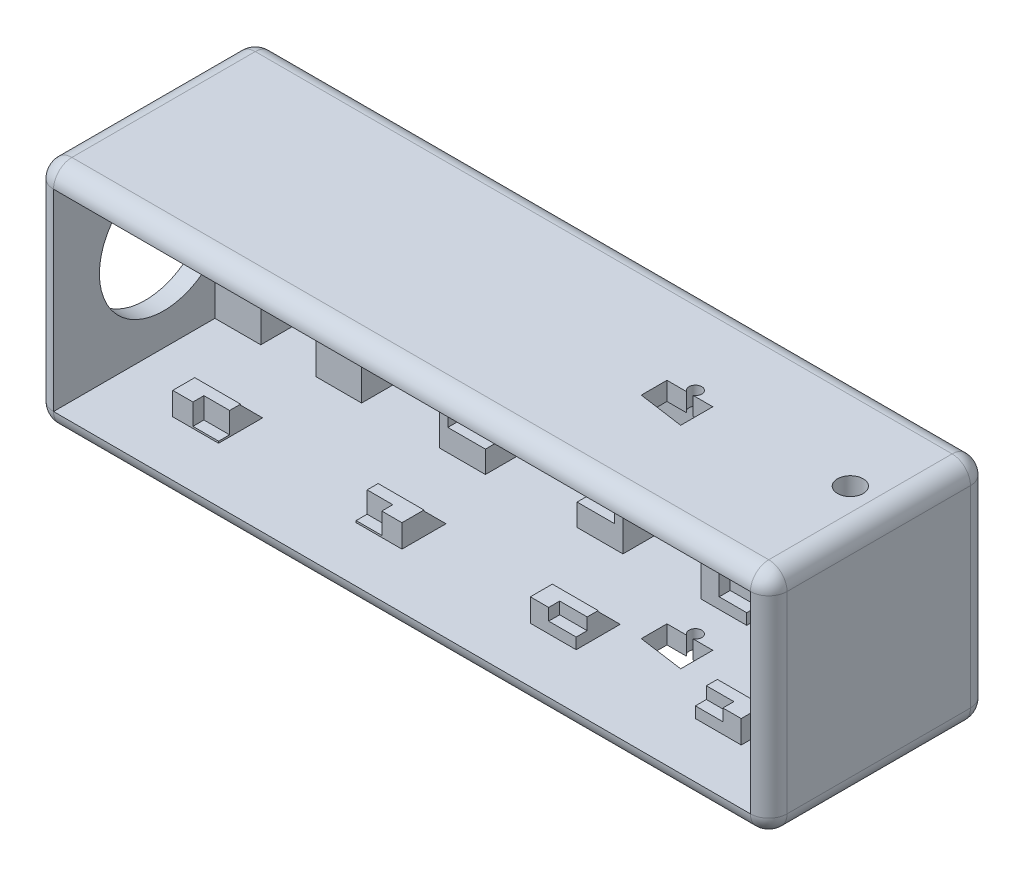
SolidWorks part; units mm, degrees
ref_plane "Front Plane" through (0, 0, 0) normal (1, 0, 0) x (0, 1, 0)
ref_plane "Top Plane" through (0, 0, 0) normal (0, 0, 1) x (0, 1, 0)
ref_plane "Right Plane" through (0, 0, 0) normal (0, 1, 0) x (-1, 0, 0)
sketch "Sketch1" plane through (0, 0, 0) normal (0, 0, 1) x (0, 1, 0)
  line L0 (0, 200) -> (0, -200) construction
  line L1 (-62.5, 200) -> (62.5, 200)
  line L2 (-62.5, 200) -> (-62.5, -200)
  line L3 (-62.5, -200) -> (62.5, -200)
  line L4 (62.5, 200) -> (62.5, -200)
  line L5 (-62.5, 0) -> (62.5, 0) construction
  point P4 (0, 0)
  point P10 (0, 0)
  dimension "D1" = 125
  dimension "D2" = 400
extrude "Boss-Extrude1" add sketch "Sketch1" along normal mid plane 120
shell "Shell2" thickness 10
sketch "Sketch3" plane through (0, 52.5, 0) normal (0, -1, 0) x (1, 0, 0)
  line L0 (-190, 60) -> (-190, -50) construction
  line L1 (-155, 30) -> (-30, 30) construction
  line L2 (-155, 30) -> (-155, 18)
  line L3 (-155, 18) -> (-30, 18) construction
  line L4 (-30, 30) -> (-30, 18)
  line L6 (-190, -28) -> (-110, -28) construction
  line L7 (-190, -28) -> (-190, -40)
  line L8 (-190, -40) -> (-110, -40) construction
  line L9 (-110, -28) -> (-110, -40)
  line L10 (190, 60) -> (-190, 60) construction
  line L11 (190, 60) -> (190, -50) construction
  line L12 (40, 30) -> (155, 30) construction
  line L13 (40, 30) -> (40, 18)
  line L14 (40, 18) -> (155, 18) construction
  line L15 (155, 30) -> (155, 18)
  line L16 (-110, -34) -> (-67.5, -34) construction
  line L17 (75, -28) -> (190, -28) construction
  line L18 (75, -28) -> (75, -40)
  line L19 (75, -40) -> (190, -40) construction
  line L20 (190, -28) -> (190, -40)
  line L21 (32.5, -40) -> (-67.5, -40) construction
  line L22 (32.5, -40) -> (32.5, -28)
  line L23 (32.5, -28) -> (-67.5, -28) construction
  line L24 (-67.5, -40) -> (-67.5, -28)
  line L25 (32.5, -34) -> (75, -34) construction
  line L26 (-155, 30) -> (-130, 30)
  line L27 (-130, 30) -> (-130, 18)
  line L28 (-130, 18) -> (-155, 18)
  line L29 (-30, 30) -> (-55, 30)
  line L30 (-55, 30) -> (-55, 18)
  line L31 (-55, 18) -> (-30, 18)
  line L32 (-110, -28) -> (-135, -28)
  line L33 (-135, -28) -> (-135, -40)
  line L34 (-135, -40) -> (-110, -40)
  line L35 (-190, -28) -> (-165, -28)
  line L36 (-165, -28) -> (-165, -40)
  line L37 (-165, -40) -> (-190, -40)
  line L38 (-67.5, -28) -> (-42.5, -28)
  line L39 (-42.5, -28) -> (-42.5, -40)
  line L40 (-42.5, -40) -> (-67.5, -40)
  line L41 (32.5, -28) -> (7.5, -28)
  line L42 (7.5, -28) -> (7.5, -40)
  line L43 (7.5, -40) -> (32.5, -40)
  line L44 (190, -28) -> (165, -28)
  line L45 (165, -28) -> (165, -40)
  line L46 (165, -40) -> (190, -40)
  line L47 (75, -40) -> (100, -40)
  line L48 (100, -40) -> (100, -28)
  line L49 (100, -28) -> (75, -28)
  line L50 (155, 18) -> (130, 18)
  line L51 (130, 18) -> (130, 30)
  line L52 (130, 30) -> (155, 30)
  line L53 (40, 30) -> (65, 30)
  line L54 (65, 30) -> (65, 18)
  line L55 (65, 18) -> (40, 18)
  line L56 (-200, -60) -> (200, -60) construction
  dimension "D1" = 125
  dimension "D2" = 12
  dimension "D3" = 35
  dimension "D4" = 80
  dimension "D5" = 20
  dimension "D6" = 0
  dimension "D7" = 30
  dimension "D8" = 35
  dimension "D9" = 100
  dimension "D10" = 115
  dimension "D11" = 0
  dimension "D12" = 115
  dimension "D13" = 12
  dimension "D14" = 25
extrude "Boss-Extrude2" add sketch "Sketch3" along normal up to next
sketch "Linear Pattern Help" plane through (0, 52.5, 0) normal (0, -1, 0) x (1, 0, 0)
  line L0 (180, -50) -> (180, 60)
  line L1 (190, -50) -> (-190, -50) construction
  line L2 (190, 60) -> (-190, 60) construction
  line L3 (190, 60) -> (190, -28) construction
  dimension "D1" = 10
sketch "Adrian PCB" plane through (0, 0, 30) normal (0, 0, 1) x (1, 0, 0)
  line L0 (-138.0598, 52.5) -> (-138.0598, 51.5) construction
  line L1 (-144, 51.5) -> (-41, 51.5)
  line L2 (-144, 51.5) -> (-144, -51.5)
  line L3 (-144, -51.5) -> (-41, -51.5)
  line L4 (-41, 51.5) -> (-41, -51.5)
  line L5 (-130, 52.5) -> (-155, 52.5) construction
  line L6 (-136.4669, -51.5) -> (-136.4669, -52.5) construction
  line L7 (-190, -52.5) -> (190, -52.5) construction
  line L8 (-144, 41.7033) -> (-155, 41.7033) construction
  line L9 (-155, -52.5) -> (-155, 52.5) construction
  line L10 (-41, 39.9776) -> (-30, 39.9776) construction
  line L11 (-30, -52.5) -> (-30, 52.5) construction
  dimension "D1" = 103
sketch "Sketch10" plane through (0, 0, 30) normal (0, 0, 1) x (1, 0, 0)
  line L0 (-155, -52.5) -> (-155, 52.5) construction
  line L1 (-155, 40) -> (155, 40)
  line L2 (-155, 40) -> (-155, -40)
  line L3 (-155, -40) -> (155, -40)
  line L4 (155, 40) -> (155, -40)
  line L5 (155, -52.5) -> (155, 52.5) construction
  line L6 (-147.038, 40) -> (-147.038, 52.5) construction
  line L7 (190, 52.5) -> (-190, 52.5) construction
  line L8 (-148.376, -40) -> (-148.376, -52.5) construction
  line L9 (-190, -52.5) -> (190, -52.5) construction
  dimension "D1" = 80
extrude "Center Top Extrude" cut sketch "Sketch10" against normal up to next
sketch "Dirks PCB" plane through (0, 0, 30) normal (0, 0, 1) x (1, 0, 0)
  line L0 (56.7566, 46.5) -> (56.7566, 52.5) construction
  line L1 (50, 46.5) -> (145, 46.5)
  line L2 (50, 46.5) -> (50, -46.5)
  line L3 (50, -46.5) -> (145, -46.5)
  line L4 (145, 46.5) -> (145, -46.5)
  line L5 (190, 52.5) -> (-190, 52.5) construction
  line L6 (60.8982, -46.5) -> (60.8982, -52.5) construction
  line L7 (40, -52.5) -> (65, -52.5) construction
  line L8 (50, 43.3526) -> (40, 43.3526) construction
  line L9 (40, 40) -> (40, 52.5) construction
  line L10 (145, 43.3526) -> (155, 43.3526) construction
  line L11 (155, 40) -> (155, 52.5) construction
  dimension "D1" = 95
  dimension "D2" = 93
extrude "Dirks Extrued" cut sketch "Dirks PCB" against normal blind 6
extrude "Adrian Extrude" cut sketch "Adrian PCB" against normal blind 6
sketch "Center Bottom Sketch" plane through (0, 0, -28) normal (0, 0, 1) x (1, 0, 0)
  line L0 (-46.618, 35) -> (-46.618, 52.5) construction
  line L1 (-67.5, 35) -> (190, 35)
  line L2 (-67.5, 35) -> (-67.5, -35)
  line L3 (-67.5, -35) -> (190, -35)
  line L4 (190, 35) -> (190, -35)
  line L5 (-42.5, 52.5) -> (-67.5, 52.5) construction
  line L6 (-51.9538, -35) -> (-51.9538, -52.5) construction
  line L7 (-67.5, -52.5) -> (-42.5, -52.5) construction
  line L8 (-67.5, -52.5) -> (-67.5, 52.5) construction
  line L9 (190, -52.5) -> (190, 52.5) construction
  dimension "D1" = 70
extrude "Center Bottom Extrude" cut sketch "Center Bottom Sketch" against normal up to next
sketch "Andrew PCB" plane through (0, 0, -28) normal (0, 0, 1) x (1, 0, 0)
  line L0 (97.7578, 46.5) -> (97.7578, 52.5) construction
  line L1 (85, 46.5) -> (175, 46.5)
  line L2 (85, 46.5) -> (85, -46.5)
  line L3 (85, -46.5) -> (175, -46.5)
  line L4 (175, 46.5) -> (175, -46.5)
  line L5 (100, 52.5) -> (75, 52.5) construction
  line L6 (89.3826, -46.5) -> (89.3826, -52.5) construction
  line L7 (75, -52.5) -> (100, -52.5) construction
  line L8 (85, -43.4086) -> (75, -43.4086) construction
  line L9 (75, -52.5) -> (75, -35) construction
  line L10 (190, 35) -> (190, 52.5) construction
  dimension "D1" = 90
  dimension "D2" = 93
  dimension "D3" = 15
extrude "Andrew Extrude" cut sketch "Andrew PCB" against normal blind 6
sketch "Sam PCB" plane through (0, 0, -28) normal (0, 0, 1) x (1, 0, 0)
  line L0 (-55.844, 40.5) -> (-55.844, 52.5) construction
  line L1 (-63, 40.5) -> (28, 40.5)
  line L2 (-63, 40.5) -> (-63, -40.5)
  line L3 (-63, -40.5) -> (28, -40.5)
  line L4 (28, 40.5) -> (28, -40.5)
  line L5 (-42.5, 52.5) -> (-67.5, 52.5) construction
  line L6 (-60.3574, -40.5) -> (-60.3574, -52.5) construction
  line L7 (-67.5, -52.5) -> (-42.5, -52.5) construction
  line L8 (28, -36.9296) -> (32.5, -36.9296) construction
  line L9 (32.5, -52.5) -> (32.5, -35) construction
  line L10 (-67.5, -37.9586) -> (-63, -37.9586) construction
  line L11 (-67.5, -52.5) -> (-67.5, -35) construction
  dimension "D1" = 91
  dimension "D2" = 81
extrude "Sam Extrude" cut sketch "Sam PCB" against normal blind 6
sketch "Mo Pcb" plane through (0, 0, -28) normal (0, 0, 1) x (1, 0, 0)
  line L1 (-181.1363, 29.3176) -> (-117.1363, 29.3176)
  line L2 (-181.1363, 29.3176) -> (-181.1363, -30.6824)
  line L3 (-181.1363, -30.6824) -> (-117.1363, -30.6824)
  line L4 (-117.1363, 29.3176) -> (-117.1363, -30.6824)
  dimension "D1" = 64
  dimension "D2" = 60
sketch "Glass Dome Sketch" plane through (-200, 0, 0) normal (-1, 0, 0) x (0, -1, 0)
  circle A0 centre (0, 0) radius 35
  dimension "D1" = 70
fillet "Fillet1" radius 10 13 edges at (0, 62.5, 60) (0, 62.5, -60) (200, 0, 60) (200, 62.5, 0) (200, 0, -60) (0, -62.5, 60) (200, -62.5, 0) (0, -62.5, -60) (-200, 62.5, 0) (-200, 0, 60) (-200, -62.5, 0) (-200, 0, -60) (-42.5, 46.5, -28)
extrude "Dome Cut/Slot" cut sketch "Glass Dome Sketch" against normal up to surface (10 mm away) up to face at (-190, 0, 16)
extrude "Cut-Extrude2" cut sketch "Mo Pcb" against normal blind 6
chamfer "Chamfer1" distance 12 angle 45 12 edges at (-122.5, 52.5, -40) (-177.5, 52.5, -40) (-122.5, -52.5, -40) (-177.5, -52.5, -40) (142.5, 52.5, 18) (52.5, 52.5, 18) (-42.5, 52.5, 18) (-142.5, 52.5, 18) (-142.5, -52.5, 18) (-42.5, -52.5, 18) (52.5, -52.5, 18) (142.5, -52.5, 18)
chamfer "Chamfer2" distance 18 angle 45 8 edges at (20, 52.5, -40) (87.5, -52.5, -40) (87.5, 52.5, -40) (177.5, 52.5, -40) (177.5, -52.5, -40) (-55, -52.5, -40) (-55, 52.5, -40) (20, -52.5, -40)
sketch "Motor Cutout" plane through (0, -62.5, 0) normal (0, -1, 0) x (1, 0, 0)
  line L0 (0, 0) -> (90, 0) construction
  line L1 (77.5, -7) -> (88.1972, -7)
  line L2 (77.5, -7) -> (77.5, 7)
  line L3 (77.5, 7) -> (102.5, 7)
  line L4 (102.5, -7) -> (102.5, 7)
  line L5 (77.5, -7) -> (102.5, 7) construction
  line L6 (77.5, 7) -> (102.5, -7) construction
  line L7 (90, 0) -> (90, -10) construction
  line L8 (91.8028, -7) -> (102.5, -7)
  line L9 (77.5, 7) -> (102.5, 10.5135)
  line L10 (102.5, 10.5135) -> (102.5, 7)
  arc A1 (88.1972, -7) -> (91.8028, -7) centre (90, -10) ccw
  dimension "D1" = 90
  dimension "D4" = 7
  dimension "D2" = 25
  dimension "D3" = 14
  dimension "D5" = 10
  dimension "D6" = 8
extrude "Cut-Extrude3" cut sketch "Motor Cutout" against normal through all both and the other way through all contours L10 L9 L3 | L1 A1 L8 L4 L3 L2
sketch "Sketch11" plane through (0, 62.5, 0) normal (0, 1, 0) x (1, 0, 0)
  line L0 (102.5, 7) -> (177.5, 7) construction
  circle A0 centre (177.5, 7) radius 7
  dimension "D2" = 14
  dimension "D1" = 75
extrude "Cut-Extrude4" cut sketch "Sketch11" against normal blind 10 and the other way through all
sketch "Sketch12" plane through (0, -62.5, 0) normal (0, -1, 0) x (1, 0, 0)
  line L0 (0, -91.3264) -> (0, -15.2485) construction
  line L1 (-0.3, 91.3264) -> (-0.3, 35.3)
  line L2 (-0.3, 34.8757) -> (-10, 44.5757)
  line L3 (-10, 44.5757) -> (-10, 9.5757)
  line L4 (-10, 9.5757) -> (0, 19.5757)
  line L5 (0.3, 19.8757) -> (0.3, -15.1243)
  line L7 (-10.3, -4.5243) -> (-10.3, -39.5243)
  line L8 (-10.3, -39.5243) -> (-0.3, -29.5243)
  line L9 (-0.3, -29.5243) -> (-0.3, -79.96)
  line L10 (-0.3, -79.96) -> (0, -79.96)
  line L11 (0, -79.96) -> (0, -28.8)
  line L12 (0, -28.8) -> (-10, -38.8)
  line L13 (-10, -38.8) -> (-10, -5.2485)
  line L16 (0, 20) -> (-9.7, 10.3)
  line L17 (-9.7, 10.3) -> (-9.7, 44.7)
  line L18 (-9.7, 44.7) -> (-0.3, 35.3)
  line L19 (0, 35) -> (0, 91.3264)
  line L20 (0, 91.3264) -> (-0.3, 91.3264)
  line L21 (-10, -5.2485) -> (0, -15.2485)
  line L22 (0, -14.8243) -> (-10.3, -4.5243)
  line L23 (-190, 50) -> (190, 50) construction
  line L24 (0, -15.2485) -> (0.3, -15.5485)
  line L25 (0.3, -15.5485) -> (0.3, -15.1243)
  line L26 (0, 20) -> (0.3, 20.3)
  line L27 (0, -14.8243) -> (0, 19.5757) construction
  line L28 (0, -14.8243) -> (0, 19.5757)
  line L29 (0.3, 20.3) -> (0.3, 19.8757)
  line L30 (-0.3, 34.8757) -> (0, 34.5757)
  line L31 (0, 34.5757) -> (0, 35)
  line L32 (0, 20) -> (0, 91.3264) construction
  line L34 (-215.6836, 79.96) -> (215.6836, 79.96)
  line L35 (-215.6836, 79.96) -> (-215.6836, -79.96)
  line L36 (-215.6836, -79.96) -> (215.6836, -79.96)
  line L37 (215.6836, 79.96) -> (215.6836, -79.96)
  line L38 (-215.6836, 79.96) -> (215.6836, -79.96) construction
  line L39 (-215.6836, -79.96) -> (215.6836, 79.96) construction
  point P4 (0, 0)
  point P7 (-10, 27.0757)
  point P32 (0, 0)
  dimension "D1" = 0.3
  dimension "D2" = 0.3
  dimension "D3" = 0.3
  dimension "D6" = 0.3
  dimension "D7" = 0.3
  dimension "D8" = 0.3
  dimension "D9" = 0.3
  dimension "D11" = 10
  dimension "D12" = 45
  dimension "D4" = 35
  dimension "D13" = 35
  dimension "D14" = 0.3
  dimension "D15" = 45
  dimension "D16" = 35
  dimension "D17" = 15
equation "\"Tolerance\"=0.3"
equation "\"D3@Sketch12\"=\"Tolerance\""
equation "\"D2@Sketch12\"=\"Tolerance\""
equation "\"D1@Sketch12\"=\"Tolerance\""
equation "\"D6@Sketch12\"=\"Tolerance\""
equation "\"D7@Sketch12\"=\"Tolerance\""
equation "\"D8@Sketch12\"=\"Tolerance\""
equation "\"D14@Sketch12\"=\"Tolerance\""
